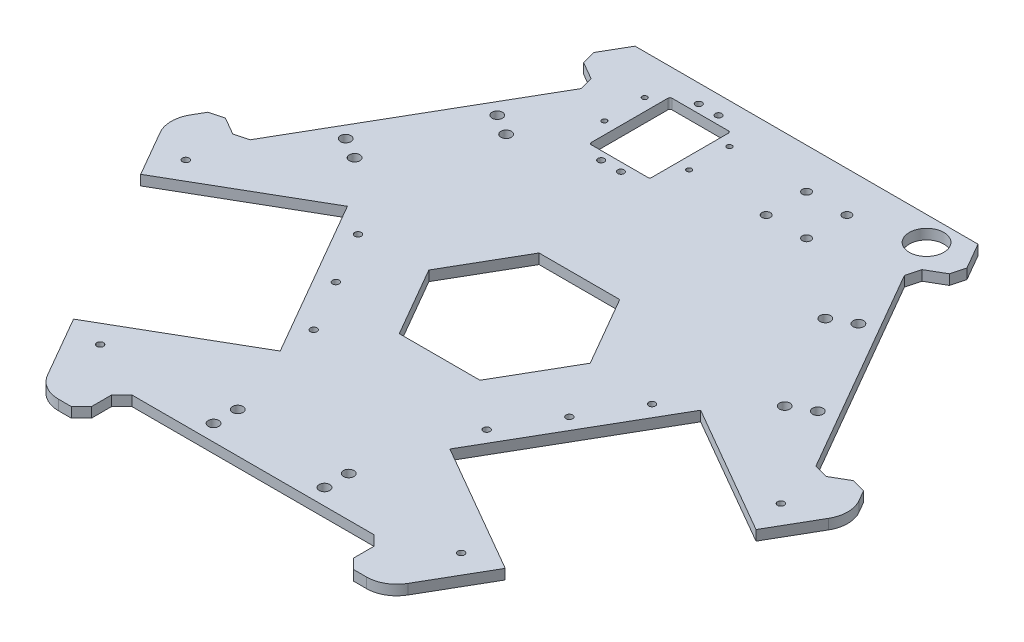
SolidWorks part; units mm, degrees
material "5052-O"
ref_plane "前基準面" through (0, 0, 0) normal (0, 0, 1) x (1, 0, 0)
ref_plane "上基準面" through (0, 0, 0) normal (0, 1, 0) x (1, 0, 0)
ref_plane "右基準面" through (0, 0, 0) normal (1, 0, 0) x (0, 0, -1)
sketch "草圖1" plane through (0, 0, 0) normal (0, 1, 0) x (1, 0, 0)
  line L1 (85, 147.2243) -> (-85, 147.2243)
  line L2 (-85, 147.2243) -> (-170, 0)
  line L3 (-170, 0) -> (-85, -147.2243)
  line L4 (-85, -147.2243) -> (85, -147.2243)
  line L5 (85, -147.2243) -> (170, 0)
  line L6 (170, 0) -> (85, 147.2243)
  circle A0 centre (0, 0) radius 147.2243 construction
  dimension "D1" = 170
extrude "填料-伸長1" add sketch "草圖1" along normal blind 5
ref_axis "基準軸1" through (0, -0.25, 0) along (0, 1, 0)
sketch "草圖46" plane through (0, 5, 0) normal (0, 1, 0) x (1, 0, 0)
  line L0 (-65, -147.2243) -> (65, -147.2243)
  line L1 (-65, -147.2243) -> (-65, -127.2243)
  line L2 (65, -147.2243) -> (65, -127.2243)
  line L3 (-65, -127.2243) -> (65, -127.2243)
  line L4 (-85, -147.2243) -> (85, -147.2243) construction
  point P6 (0, -147.2243)
  point P7 (0, -147.2243)
  dimension "D1" = 20
  dimension "D2" = 130
extrude "除料-伸長31" cut sketch "草圖46" against normal up to next
sketch "草圖8" plane through (0, 5, 0) normal (0, 1, 0) x (1, 0, 0)
  line L0 (65, -127.2243) -> (-65, -127.2243) construction
  line L2 (-27.5, -107.2243) -> (27.5, -107.2243) construction
  line L3 (-27.5, -107.2243) -> (-27.5, -119.2243) construction
  line L4 (-27.5, -119.2243) -> (27.5, -119.2243) construction
  line L5 (27.5, -107.2243) -> (27.5, -119.2243) construction
  circle A0 centre (-27.5, -119.2243) radius 2.6
  circle A1 centre (27.5, -119.2243) radius 2.6
  circle A2 centre (-27.5, -107.2243) radius 2.6
  circle A3 centre (27.5, -107.2243) radius 2.6
  point P7 (0, -119.2243)
  point P14 (0, -127.2243)
  dimension "D3" = 5.2
  dimension "D1" = 55
  dimension "D2" = 12
  dimension "D4" = 8
extrude "除料-伸長6" cut sketch "草圖8" against normal through all
pattern_circular "環狀複製排列1" count 3 over 360 about axis through (0, -0.25, 0) along (0, 1, 0) of "除料-伸長6", "除料-伸長31"
chamfer "導角1" distance 5 angle 45 12 edges at (65, 2.5, 127.2243) (65, 2.5, 147.2243) (-65, 2.5, 147.2243) (-65, 2.5, 127.2243) (77.6795, 2.5, -119.9038) (95, 2.5, -129.9038) (160, 2.5, -17.3205) (142.6795, 2.5, -7.3205) (-160, 2.5, -17.3205) (-142.6795, 2.5, -7.3205) (-77.6795, 2.5, -119.9038) (-95, 2.5, -129.9038)
sketch "草圖5" plane through (0, 5, 0) normal (0, 1, 0) x (1, 0, 0)
  line L0 (-152.5, -30.3109) -> (-107, -109.1192)
  line L1 (-152.5, -30.3109) -> (-87.5481, 7.1891)
  line L2 (-107, -109.1192) -> (-42.0481, -71.6192)
  line L3 (-87.5481, 7.1891) -> (-42.0481, -71.6192)
  line L4 (-170, 0) -> (-85, -147.2243) construction
  dimension "D1" = 75
  dimension "D2" = 91
  dimension "35" = 35
extrude "除料-伸長4" cut sketch "草圖5" against normal through all
sketch "草圖9" plane through (0, 5, 0) normal (0, 1, 0) x (1, 0, 0)
  line L0 (-64.7981, -32.215) -> (-118.4917, -63.215) construction
  line L1 (-42.0481, -71.6192) -> (-87.5481, 7.1891) construction
  line L2 (-118.4917, -63.215) -> (-89.4917, -113.4445) construction
  line L3 (-118.4917, -63.215) -> (-147.4917, -12.9856) construction
  circle A0 centre (-89.4917, -113.4445) radius 1.65
  circle A1 centre (-147.4917, -12.9856) radius 1.65
  dimension "D2" = 3.3
  dimension "D1" = 58
  dimension "D3" = 62
  dimension "D4" = 58
extrude "除料-伸長7" cut sketch "草圖9" against normal through all
mirror "鏡射1" about plane through (0, 0, 0) normal (1, 0, 0) of "除料-伸長4", "除料-伸長7"
fillet "圓角1" radius 15 4 edges at (170, 2.5, 0) (85, 2.5, 147.2243) (-170, 2.5, 0) (-85, 2.5, 147.2243)
sketch "草圖36" plane through (0, 5, 0) normal (0, 1, 0) x (1, 0, 0)
  line L0 (-72.8699, -2.2343) -> (-57.8699, -28.215) construction
  line L1 (-42.0481, -71.6192) -> (-87.5481, 7.1891) construction
  line L2 (-42.8699, -54.1958) -> (-57.8699, -28.215) construction
  line L3 (-57.8699, -28.215) -> (-64.7981, -32.215) construction
  circle A0 centre (-57.8699, -28.215) radius 1.25
  circle A1 centre (-42.8699, -54.1958) radius 1.25
  circle A2 centre (-72.8699, -2.2343) radius 1.25
  point P7 (-50.3699, -41.2054)
  point P10 (-64.7981, -32.215)
  dimension "D3" = 2.5
  dimension "D1" = 30
  dimension "D2" = 30
  dimension "D4" = 8
hole_wizard "M4x0.7 螺紋孔4" positions "草圖40" profile "草圖41" tap size "M4x0.7" standard "Ansi Metric" end condition through all
sketch "草圖40" plane through (0, 5, 0) normal (0, 1, 0) x (1, 0, 0)
  point P0 (-72.8699, -2.2343)
  point P3 (-57.8699, -28.215)
  point P6 (-42.8699, -54.1958)
sketch "草圖41" plane through (-72.8699, 5, 2.2343) normal (1, 0, 0) x (0, 0, 1)
  line L0 (0, 0) -> (0, 5)
  line L1 (0, 5) -> (1.65, 5)
  line L2 (1.65, 5) -> (1.65, 0)
  line L5 (1.65, 0) -> (0, 0)
  line L11 (0, -6.35) -> (0, 107.95) construction
  dimension "貫穿螺孔鑽直徑" = 3.3
  dimension "貫穿螺孔鑽深度" = 5
cosmetic thread "鑽孔螺紋1" parameters "D1"=10, "D2"=4.3
cosmetic thread "鑽孔螺紋2" parameters "D1"=10, "D2"=4.3
cosmetic thread "鑽孔螺紋3" parameters "D1"=10, "D2"=4.3
mirror "鏡射2" about plane through (0, 0, 0) normal (1, 0, 0) of "M4x0.7 螺紋孔4"
sketch "草圖51" plane through (0, 5, 0) normal (0, 1, 0) x (1, 0, 0)
  line L0 (85, 147.2243) -> (-85, 147.2243) construction
  line L1 (20, 34.641) -> (-20, 34.641)
  line L2 (-20, 34.641) -> (-40, 0)
  line L3 (-40, 0) -> (-20, -34.641)
  line L4 (-20, -34.641) -> (20, -34.641)
  line L5 (20, -34.641) -> (40, 0)
  line L6 (40, 0) -> (20, 34.641)
  circle A0 centre (0, 0) radius 34.641 construction
  dimension "D1" = 40
extrude "除料-伸長35" cut sketch "草圖51" against normal up to next
sketch "草圖53" plane through (0, 5, 0) normal (0, 1, 0) x (1, 0, 0)
  line L0 (85, 147.2243) -> (-85, 147.2243) construction
  line L1 (20, 127.2243) -> (40, 127.2243) construction
  line L2 (20, 127.2243) -> (20, 107.2243) construction
  line L3 (20, 107.2243) -> (40, 107.2243) construction
  line L4 (40, 127.2243) -> (40, 107.2243) construction
  line L5 (20, 127.2243) -> (-85, 127.2243) construction
  line L6 (-85, 127.2243) -> (-85, 147.2243) construction
  circle A0 centre (20, 127.2243) radius 2.1
  dimension "D4" = 4.2
  dimension "D1" = 20
  dimension "D2" = 20
  dimension "D3" = 20
  dimension "D5" = 90
  dimension "D6" = 105
extrude "除料-伸長37" cut sketch "草圖53" against normal up to next
pattern_linear "直線複製排列1" count 2 spacing 20 along (1, 0, 0) count 2 spacing 20 along (0, 0, 1) of "除料-伸長37"
sketch "草圖54" plane through (0, 5, 0) normal (0, 1, 0) x (1, 0, 0)
  circle A0 centre (71.5, 135.2243) radius 8.55
  circle A1 centre (40, 127.2243) radius 2.1 construction
  dimension "D1" = 17.1
  dimension "D2" = 31.5
  dimension "D3" = 8
extrude "除料-伸長38" cut sketch "草圖54" against normal up to next
sketch "草圖56" plane through (0, 0, 0) normal (0, -1, 0) x (-1, 0, 0)
  line L0 (-85, 147.2243) -> (85, 147.2243) construction
  line L2 (34.6, 89.8243) -> (34.6, 138.2243) construction
  line L3 (34.6, 138.2243) -> (44.4, 138.2243) construction
  line L4 (44.4, 138.2243) -> (44.4, 89.8243) construction
  circle A0 centre (34.6, 138.2243) radius 1.6
  circle A1 centre (44.4, 138.2243) radius 1.6
  circle A2 centre (44.4, 89.8243) radius 1.6
  circle A3 centre (34.6, 89.8243) radius 1.6
  point P2 (0, 147.2243)
  point P5 (39.5, 138.2243)
  dimension "D1" = 3.2
  dimension "D2" = 9
  dimension "D3" = 39.5
  dimension "D6" = 48.4
  dimension "D7" = 9.8
  dimension "D4" = 2
  dimension "D5" = 2
extrude "除料-伸長40" cut sketch "草圖56" against normal blind 10 contours A3 | A2 | A1 | A0
sketch "草圖55" plane through (0, 5, 0) normal (0, 1, 0) x (1, 0, 0)
  line L1 (-24.5, 134.0243) -> (-54.5, 134.0243)
  line L2 (-24.5, 134.0243) -> (-24.5, 94.0243)
  line L3 (-24.5, 94.0243) -> (-54.5, 94.0243)
  line L4 (-54.5, 134.0243) -> (-54.5, 94.0243)
  line L5 (85, 147.2243) -> (-85, 147.2243) construction
  circle A2 centre (-34.6, 138.2243) radius 1.6 construction
  point P6 (-39.5, 134.0243)
  point P9 (0, 147.2243)
  dimension "D3" = 4.2
  dimension "D1" = 40
  dimension "D2" = 30
  dimension "D4" = 39.5
extrude "除料-伸長39" cut sketch "草圖55" against normal blind 10 contours L2 L1 L4 L3
fillet "圓角2" radius 1 4 edges at (-54.5, 2.5, -94.0243) (-24.5, 2.5, -94.0243) (-24.5, 2.5, -134.0243) (-54.5, 2.5, -134.0243)
hole_wizard "M3x0.5 螺紋孔1" positions "草圖58" profile "草圖59" tap size "M3x0.5" standard "Ansi Metric"
sketch "草圖58" plane through (0, 5, 0) normal (0, 1, 0) x (1, 0, 0)
  line L1 (-60.5, 127.5243) -> (-18.5, 127.5243) construction
  line L2 (-60.5, 127.5243) -> (-60.5, 107.5243) construction
  line L3 (-60.5, 107.5243) -> (-18.5, 107.5243) construction
  line L4 (-18.5, 127.5243) -> (-18.5, 107.5243) construction
  line L5 (-25.5, 134.0243) -> (-53.5, 134.0243) construction
  point P0 (-60.5, 127.5243)
  point P2 (-60.5, 107.5243)
  point P4 (-18.5, 107.5243)
  point P6 (-18.5, 127.5243)
  point P110 (-39.5, 127.5243)
  point P113 (-39.5, 134.0243)
  dimension "D1" = 20
  dimension "D2" = 42
  dimension "D3" = 6.5
sketch "草圖59" plane through (-60.5, 5, -127.5243) normal (1, 0, 0) x (0, 0, 1)
  line L0 (0, 0) -> (0, 9.2511)
  line L1 (0, 9.2511) -> (1.25, 8.5)
  line L2 (1.25, 8.5) -> (1.25, 0)
  line L5 (1.25, 0) -> (0, 0)
  line L10 (0, 9.2511) -> (-1.25, 8.5) construction
  line L11 (0, -6.35) -> (0, 107.95) construction
  dimension "螺孔鑽直徑" = 2.5
  dimension "螺孔鑽深度" = 8.5
  dimension "導頭角度" = 118
cosmetic thread "鑽孔螺紋4" parameters "D1"=6, "D2"=3
cosmetic thread "鑽孔螺紋5" parameters "D1"=6, "D2"=3
cosmetic thread "鑽孔螺紋6" parameters "D1"=6, "D2"=3
cosmetic thread "鑽孔螺紋7" parameters "D1"=6, "D2"=3
